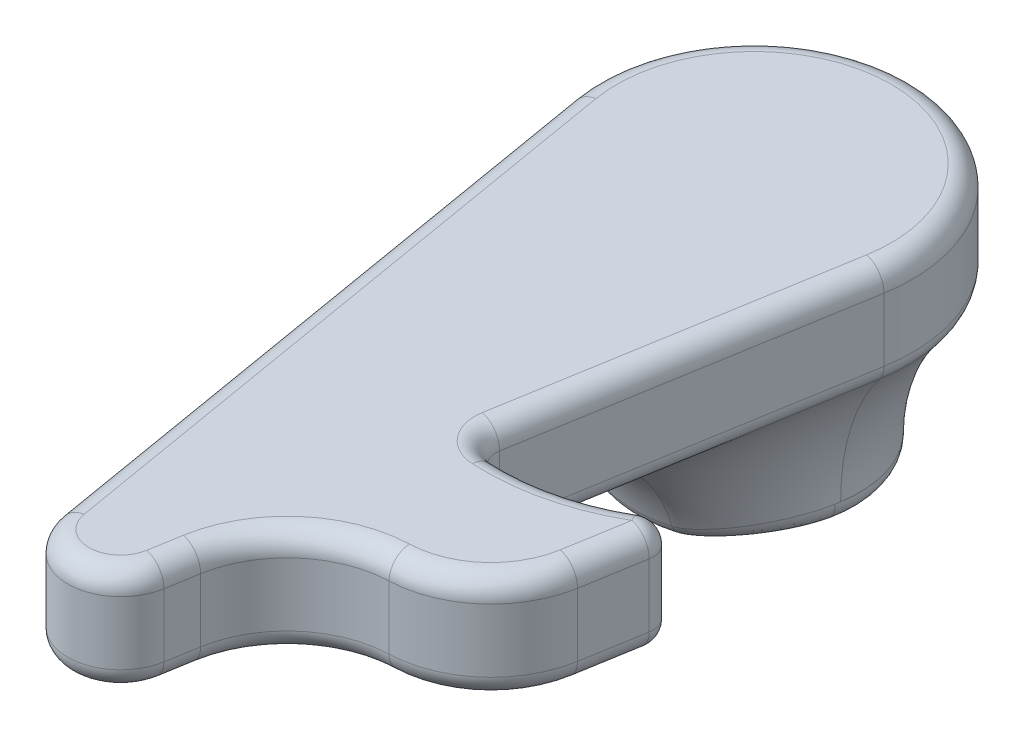
SolidWorks part; units mm, degrees
ref_plane "Front Plane" through (0, 0, 0) normal (0, 0, 1) x (1, 0, 0)
ref_plane "Top Plane" through (0, 0, 0) normal (0, 1, 0) x (1, 0, 0)
ref_plane "Right Plane" through (0, 0, 0) normal (1, 0, 0) x (0, 0, -1)
sketch "Sketch1" plane through (0, 0, 0) normal (0, 1, 0) x (1, 0, 0)
  circle A1 centre (0, 0) radius 5
  dimension "D3" = 10
extrude "Boss-Extrude1" add sketch "Sketch1" along normal blind 12
sketch "Sketch2" plane through (0, 0, 0) normal (0, -1, 0) x (1, 0, 0)
  line L1 (-2.6552, 1.6) -> (2.6552, 1.6)
  arc A1 (-2.6552, 1.6) -> (2.6552, 1.6) centre (0, 0) ccw
  dimension "D1" = 6.2
  dimension "D2" = 1.6
extrude "Cut-Extrude1" cut sketch "Sketch2" against normal blind 6.5
sketch "Sketch3" plane through (0, 12, 0) normal (0, 1, 0) x (1, 0, 0)
  line L0 (0, 0) -> (0, -30) construction
  line L1 (-7.3951, -1.25) -> (-2.465, -30.4167)
  line L2 (7.3951, -1.25) -> (2.465, -30.4167)
  arc A0 (7.3951, -1.25) -> (-7.3951, -1.25) centre (0, 0) ccw
  arc A1 (-2.465, -30.4167) -> (2.465, -30.4167) centre (0, -30) ccw
  dimension "D1" = 15
  dimension "D2" = 5
  dimension "D3" = 30
extrude "Boss-Extrude2" add sketch "Sketch3" against normal blind 5
sketch "Sketch4" plane through (0, 12, 0) normal (0, 1, 0) x (1, 0, 0)
  line L0 (2.465, -30.4167) -> (7.3951, -1.25) construction
  line L1 (3.5496, -24) -> (11.4378, -25.3333)
  line L2 (11.4378, -25.3333) -> (13.1422, -15.2494)
  line L3 (3.5496, -24) -> (4.5875, -17.8601)
  arc A0 (4.5875, -17.8601) -> (13.1422, -15.2494) centre (6.2541, -8) ccw
  dimension "D3" = 20
  dimension "D1" = 8
  dimension "D2" = 24
  dimension "D4" = 8
extrude "Boss-Extrude3" add sketch "Sketch4" against normal up to surface (5 mm away) up to face at (0, 7, 5)
fillet "Fillet3" radius 5 1 edges at (3.5496, 9.5, 24)
fillet "Fillet4" radius 5 1 edges at (11.4378, 9.5, 25.3333)
fillet "Fillet5" radius 1 20 edges at (9.173, 7, 17.5645) (9.173, 12, 17.5645) (5.9913, 7, 9.5551) (0, 7, -7.5) (-4.9301, 7, 15.8333) (0, 7, 32.5) (2.5907, 7, 29.6734) (4.3546, 7, 25.9999) (10.5991, 7, 23.5327) (5.9913, 12, 9.5551) (0, 12, -7.5) (-4.9301, 12, 15.8333) (0, 12, 32.5) (2.5907, 12, 29.6734) (4.3546, 12, 25.9999) (10.5991, 12, 23.5327) (13.1422, 9.5, 15.2494) (12.6898, 7, 17.9259) (12.6898, 12, 17.9259) (4.5875, 9.5, 17.8601)
fillet "Fillet1" radius 10 1 edges at (0, 7, 5)
fillet "Fillet2" radius 1 5 edges at (0, 0, 1.6) (0, 0, -3.1) (0, 0, -5) (-2.4749, 0, 4.7077) (2.2285, 0, 4.8886)
